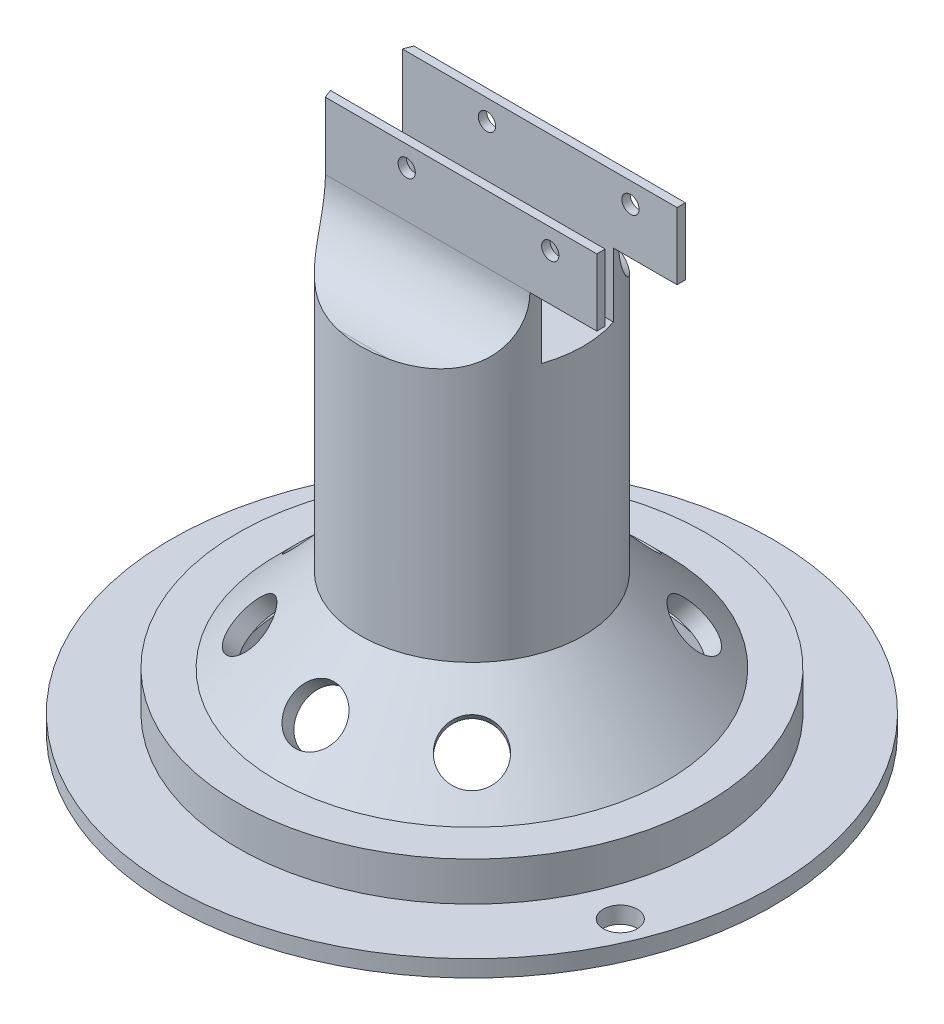
SolidWorks part; units mm, degrees
material "AISI 316 Tôle d'acier inoxydable (SS)"
ref_plane "Front Plane" through (0, 0, 0) normal (0, 0, 1) x (1, 0, 0)
ref_plane "Top Plane" through (0, 0, 0) normal (0, 1, 0) x (1, 0, 0)
ref_plane "Right Plane" through (0, 0, 0) normal (1, 0, 0) x (0, 0, -1)
sketch "Esquisse1" plane through (0, 0, 0) normal (0, 0, 1) x (1, 0, 0)
  line L2 (-42, -12) -> (-42, -15)
  line L3 (-33.7574, -15) -> (-18.7574, 0)
  line L4 (-42, -15) -> (0, -15) construction
  line L5 (0, -15) -> (0, 0) construction
  line L6 (-20, 3) -> (0, 3)
  line L7 (-18.7574, 0) -> (0, 0)
  line L9 (0, 0) -> (0, 3)
  line L10 (-42, -15) -> (-33.7574, -15)
  line L11 (-42, -12) -> (-35, -12)
  line L12 (-35, -12) -> (-20, 3)
  line L13 (-27.5, -4.5) -> (-25.3787, -6.6213) construction
  point P14 (-33.7574, -15)
  point P25 (-42, -12)
  dimension "D1" = 42
  dimension "D2" = 45
  dimension "D3" = 3
  dimension "D4" = 7
  dimension "D5" = 20
revolve "Révolution2" add sketch "Esquisse1" angle 360 about L9
sketch "Esquisse3" plane through (0, 0, 0) normal (0, 0, 1) x (1, 0, 0)
  line L0 (-20, 3) -> (-35, -12) construction
  line L2 (-42, -15) -> (42, -15) construction
  line L3 (-33.7574, -15) -> (-18.7574, 0) construction
  line L4 (-18.7574, 0) -> (18.7574, 0) construction
  line L5 (-28.9156, -4.5014) -> (-25.4507, -1.0365)
  line L6 (-25.4507, -1.0365) -> (-11.4873, -15)
  line L7 (-11.4873, -15) -> (-14.9521, -18.4648)
  line L8 (-28.9156, -4.5014) -> (-14.9521, -18.4648)
  dimension "D1" = 4.9
  dimension "D2" = 1
  dimension "D3" = 9.6047
revolve "Enlèvement de matière-Révolution1" cut sketch "Esquisse3" angle 360 about L8
pattern_circular "Répétition circulaire1" count 4 every 45 about axis through (0, 3, 0) along (0, -1, 0) of "Enlèvement de matière-Révolution1" other way count 4
sketch "Esquisse4" plane through (0, 3, 0) normal (0, 1, 0) x (1, 0, 0)
  circle A0 centre (0, 0) radius 20
extrude "Boss.-Extru.1" add sketch "Esquisse4" along normal blind 45
sketch "Esquisse5" plane through (0, 48, 0) normal (0, 1, 0) x (1, 0, 0)
  line L1 (0, -13) -> (0, 13) construction
  circle A0 centre (0, 0) radius 5.9
  circle A1 centre (0, 0) radius 38.5 construction
  point P0 (0, 0)
  point P5 (0, 13)
  point P7 (0, -13)
  point P15 (0, 0)
  point P19 (0, 0)
  dimension "D1" = 11.8
  dimension "D2" = 13
  dimension "D5" = 77
  dimension "D6" = 77
extrude "Enlèv. mat.-Extru.1" cut sketch "Esquisse5" against normal up to next
sketch "Esquisse6" plane through (0, 0, 0) normal (0, -1, 0) x (-1, 0, 0)
  circle A0 centre (0, 0) radius 16.7574
  circle A1 centre (0, 0) radius 18.7574 construction
  dimension "D1" = 2
extrude "Enlèv. mat.-Extru.2" cut sketch "Esquisse6" against normal blind 45
sketch "Esquisse7" plane through (0, 0, 0) normal (0, 0, 1) x (1, 0, 0)
  line L0 (-20, 3) -> (-24.7436, -1.7436) construction
  line L1 (-24.7436, -1.7436) -> (-22.3718, 0.6282) construction
  line L2 (-22.3718, 0.6282) -> (48.3389, -70.0825) construction
  dimension "D1" = 100
ref_plane "Plan1" through (-11.5, 11.5, 0) normal (0.7071, -0.7071, 0) x (0, 0, -1)
sketch "Esquisse8" plane through (-11.5, 11.5, 0) normal (0.7071, -0.7071, 0) x (0, 0, -1)
  circle A0 centre (0, -23.6293) radius 2.5
ref_plane "Plan2" through (45.0685, -45.0685, 0) normal (0.7071, -0.7071, 0) x (0, 0, -1)
sketch "Esquisse9" plane through (45.0685, -45.0685, 0) normal (0.7071, -0.7071, 0) x (0, 0, -1)
  circle A0 centre (0, -23.6293) radius 4.9
loft "Lissage1" [suppressed] add profiles "Esquisse9", "Esquisse8"
hole_wizard "Trou taraudé M32" [suppressed] positions "Esquisse12" profile "Esquisse13" tap size "M3" standard "ISO"
sketch "Esquisse12" plane through (0, 18, 0) normal (0, 1, 0) x (1, 0, 0)
  point P0 (0, 13)
  point P3 (0, -13)
sketch "Esquisse13" plane through (0, 18, -13) normal (1, 0, 0) x (0, 0, 1)
  line L0 (0, 0) -> (0, 3)
  line L1 (0, 3) -> (1.25, 3)
  line L2 (1.25, 3) -> (1.25, 0)
  line L5 (1.25, 0) -> (0, 0)
  line L11 (0, -6.35) -> (0, 107.95) construction
  dimension "Diamètre du trou pour taraudage jusqu'au prochain" = 2.5
  dimension "Profondeur du trou pour taraudage jusqu'au prochain" = 3
cosmetic thread "Filetage de perçage1" [suppressed] parameters "D2"=3
cosmetic thread "Filetage de perçage2" [suppressed] parameters "D2"=3
sketch "Esquisse16" plane through (0, 48, 0) normal (0, 1, 0) x (1, 0, 0)
  line L0 (-18.352, 7.95) -> (18.352, 7.95)
  line L1 (-18.9314, 6.45) -> (18.9314, 6.45)
  line L2 (-20, 0) -> (20, 0) construction
  line L3 (-18.9314, -6.45) -> (18.9314, -6.45)
  line L4 (-18.352, -7.95) -> (18.352, -7.95)
  circle A0 centre (0, 0) radius 5.9
  circle A1 centre (0, 0) radius 20
  circle M5 centre (0, 0) radius 20
  dimension "D1" = 40
  dimension "D2" = 1.5
  dimension "D3" = 6.45
extrude "Boss.-Extru.3" add sketch "Esquisse16" along normal blind 23.5 contours L1 L0 M5 | L4 L3 M5
sketch "Esquisse17" plane through (0, 0, 7.95) normal (0, 0, 1) x (1, 0, 0)
  line L0 (-18.352, 71.5) -> (18.352, 71.5) construction
  line L2 (-18.352, 71.5) -> (-18.352, 48) construction
  circle A0 centre (-3.752, 67.82) radius 1.55
  dimension "D1" = 3.68
  dimension "D2" = 3.1
  dimension "D3" = 14.6
extrude "Enlèv. mat.-Extru.3" cut sketch "Esquisse17" against normal through all
sketch "Esquisse18" plane through (0, 0, 7.95) normal (0, 0, 1) x (1, 0, 0)
  line L0 (-3.752, 67.82) -> (35.2663, 67.82) construction
  line L1 (18.352, 71.5) -> (30.352, 71.5)
  line L2 (18.352, 71.5) -> (18.352, 59.5)
  line L3 (18.352, 59.5) -> (30.352, 59.5)
  line L4 (30.352, 71.5) -> (30.352, 59.5)
  dimension "D1" = 12
  dimension "D2" = 12
extrude "Boss.-Extru.4" add sketch "Esquisse18" against normal up to surface (15.9 mm away) up to face at (-5.302, 67.82, -7.95)
sketch "Esquisse20" plane through (0, 48, 0) normal (0, 1, 0) x (1, 0, 0)
  line L0 (30.352, 7.95) -> (30.352, -7.95) construction
  line L1 (18.352, 6.45) -> (30.352, 6.45)
  line L2 (18.352, 6.45) -> (18.352, -6.45)
  line L3 (18.352, -6.45) -> (30.352, -6.45)
  line L4 (30.352, 6.45) -> (30.352, -6.45)
extrude "Enlèv. mat.-Extru.4" cut sketch "Esquisse20" along normal up to surface (23.5 mm away) up to face at (2.8514, 71.5, 0)
sketch "Esquisse21" plane through (0, 0, 7.95) normal (0, 0, 1) x (1, 0, 0)
  line L0 (-3.752, 67.82) -> (25.7085, 67.82) construction
  circle A0 centre (21.998, 67.82) radius 1.55
  circle A1 centre (-3.752, 67.82) radius 1.55 construction
  dimension "D1" = 3.1
  dimension "D2" = 25.75
extrude "Enlèv. mat.-Extru.5" cut sketch "Esquisse21" against normal through all both and the other way through all
fillet "Congé1" radius 11.5 2 edges at (0, 48, 7.95) (0, 48, -7.95)
sketch "Esquisse22" plane through (0, -15, 0) normal (0, -1, 0) x (-1, 0, 0)
  circle A1 centre (0, 0) radius 33.7574
  circle A2 centre (0, 0) radius 42
extrude "remplace entretoise" add sketch "Esquisse22" along normal blind 4
sketch "Esquisse23" plane through (0, -19, 0) normal (0, -1, 0) x (1, 0, 0)
  circle A0 centre (0, 0) radius 33
  circle A1 centre (0, 0) radius 54
  circle A2 centre (0, 0) radius 29 construction
  point P4 (0, 0)
  dimension "D1" = 66
  dimension "D2" = 108
  dimension "D3" = 58
extrude "compatible purgeur" add sketch "Esquisse23" along normal blind 3
fillet "Congé2" radius 1 1 edges at (0, -19, -33.7574)
sketch "Esquisse25" plane through (0, -22, 0) normal (0, -1, 0) x (-1, 0, 0)
  line L0 (0, 0) -> (-54, 0) construction
  line L1 (-33, 0) -> (-33, -11.0081) construction
  line L2 (16.862, 24.2058) -> (18.6651, 27.3288)
  line L3 (-29.3939, -2.5) -> (-33, -2.5)
  line L4 (-29.3939, 2.5) -> (-33, 2.5)
  line L5 (12.5319, 26.7058) -> (14.3349, 29.8288)
  line L6 (12.5319, -26.7058) -> (14.3349, -29.8288)
  line L7 (16.862, -24.2058) -> (18.6651, -27.3288)
  circle A0 centre (0, 0) radius 54 construction
  circle A1 centre (0, 0) radius 33
  circle A2 centre (0, 0) radius 29.5
  circle A3 centre (0, 0) radius 27.5
  point P25 (0, 0)
  circle M2 centre (0, 0) radius 33
  dimension "D1" = 2.5
  dimension "D2" = 66
  dimension "D3" = 59
  dimension "D4" = 2
  dimension "D5" = 3
extrude "Boss.-Extru.7" add sketch "Esquisse25" against normal blind 3 contours A2 L4 L3 M2 | A2 L2 L5 M2 | A2 L6 L7 M2 | A2 A3
sketch "Esquisse26" plane through (0, -22, 0) normal (0, -1, 0) x (1, 0, 0)
  line L0 (0, 0) -> (54, 0) construction
  line L1 (0, 0) -> (-26.7611, -64.607) construction
  line L2 (0, 0) -> (68.8859, 28.5335) construction
  circle A0 centre (0, 0) radius 54 construction
  circle A1 centre (0, 0) radius 49
  circle A3 centre (45.2991, 18.6813) radius 3.05
  dimension "D2" = 98
  dimension "D3" = 6.1
  dimension "D1" = 22.5
extrude "Enlèv. mat.-Extru.7" cut sketch "Esquisse26" against normal up to next contours A1 A3 | A1 A3
